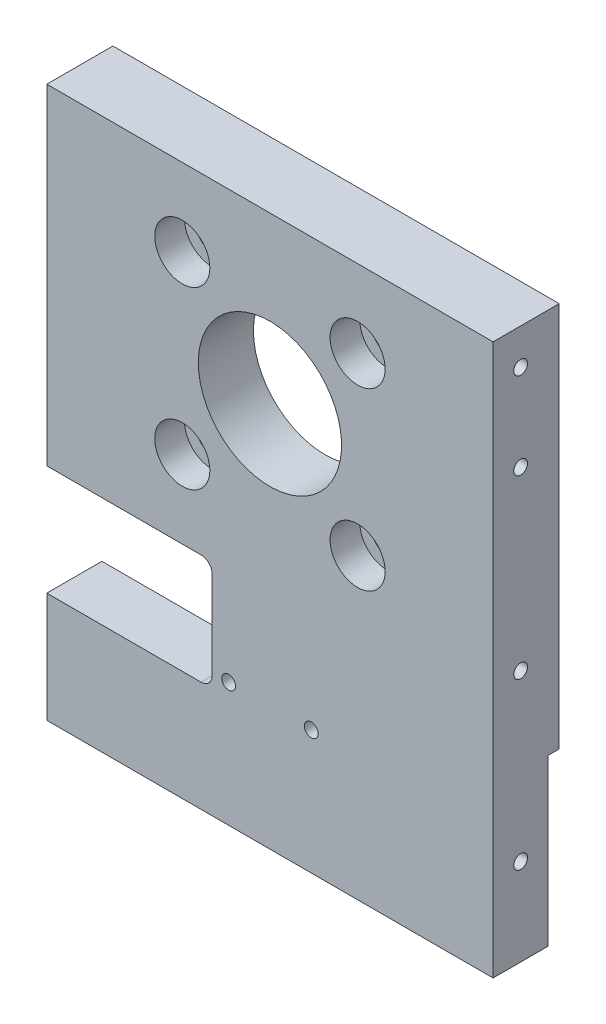
SolidWorks part; units mm, degrees
material "6061 合金"
ref_plane "前视基准面" through (0, 0, 0) normal (0, 0, 1) x (1, 0, 0)
ref_plane "上视基准面" through (0, 0, 0) normal (0, 1, 0) x (1, 0, 0)
ref_plane "右视基准面" through (0, 0, 0) normal (1, 0, 0) x (0, 0, -1)
sketch "草图1" plane through (0, 0, 0) normal (0, 0, 1) x (1, 0, 0)
  line L1 (-40.5, -50) -> (40.5, -50)
  line L2 (-40.5, -50) -> (-40.5, 50)
  line L3 (-40.5, 50) -> (40.5, 50)
  line L4 (40.5, -50) -> (40.5, 50)
  line L5 (-40.5, -50) -> (40.5, 50) construction
  line L6 (-40.5, 50) -> (40.5, -50) construction
  point P0 (0, 0)
  dimension "D1" = 81
  dimension "D2" = 100
extrude "凸台-拉伸1" add sketch "草图1" along normal blind 12
sketch "草图2" plane through (0, 0, 0) normal (0, 0, -1) x (-1, 0, 0)
  line L0 (-40.5, 50) -> (40.5, 50) construction
  circle A0 centre (0, 20) radius 13
  dimension "D1" = 26
  dimension "D2" = 30
extrude "切除-拉伸1" cut sketch "草图2" against normal through all
hole_wizard "M5 六角凹头螺钉的柱形沉头孔1" positions "草图6" profile "草图5" counterbore size "M5" standard "Iso" end condition through all
sketch "草图6" plane through (0, 0, 12) normal (0, 0, 1) x (1, 0, 0)
  line L1 (-15.9099, 4.0901) -> (15.9099, 4.0901) construction
  line L2 (-15.9099, 4.0901) -> (-15.9099, 35.9099) construction
  line L3 (-15.9099, 35.9099) -> (15.9099, 35.9099) construction
  line L4 (15.9099, 4.0901) -> (15.9099, 35.9099) construction
  line L5 (-15.9099, 4.0901) -> (15.9099, 35.9099) construction
  line L6 (-15.9099, 35.9099) -> (15.9099, 4.0901) construction
  point P0 (-15.9099, 35.9099)
  point P2 (15.9099, 35.9099)
  point P4 (15.9099, 4.0901)
  point P6 (-15.9099, 4.0901)
  point P25 (0, 20)
  dimension "D5" = 45
  dimension "D6" = 90
sketch "草图5" plane through (-15.9099, 35.9099, 12) normal (1, 0, 0) x (0, -1, 0)
  line L0 (0, 0) -> (0, 12)
  line L1 (0, 12) -> (2.75, 12)
  line L3 (2.75, 12) -> (2.75, 5.4)
  line L4 (2.75, 5.4) -> (5, 5.4)
  line L5 (5, 5.4) -> (5, 0)
  line L7 (5, 0) -> (0, 0)
  line L11 (0, -6.35) -> (0, 107.95) construction
  dimension "通孔孔直径" = 5.5
  dimension "通孔孔深度" = 12
  dimension "柱形沉头孔直径" = 10
  dimension "柱形沉头孔深度" = 5.4
hole_wizard "M3 螺纹孔1" positions "草图8" profile "草图7" tap size "M3" standard "Gb"
sketch "草图8" plane through (-40.5, 0, 0) normal (-1, 0, 0) x (0, 0, 1)
  line L0 (12, 50) -> (0, 50) construction
  line L1 (12, 50) -> (12, -50) construction
  point P0 (7, 43.5)
  point P2 (7, 27.8)
  point P4 (7, -4.2)
  point P6 (7, -34.2)
  dimension "D1" = 6.5
  dimension "D2" = 15.7
  dimension "D3" = 32
  dimension "D4" = 30
  dimension "D5" = 5
sketch "草图7" plane through (-40.5, 43.5, 7) normal (0, 1, 0) x (0, 0, 1)
  line L0 (0, 0) -> (0, 8.2511)
  line L1 (0, 8.2511) -> (1.25, 7.5)
  line L2 (1.25, 7.5) -> (1.25, 0)
  line L5 (1.25, 0) -> (0, 0)
  line L10 (0, 8.2511) -> (-1.25, 7.5) construction
  line L11 (0, -6.35) -> (0, 107.95) construction
  dimension "螺纹孔钻头直径" = 2.5
  dimension "螺纹孔钻头深度" = 7.5
  dimension "导头角度" = 118
cosmetic thread "孔螺蚊线1" parameters "D1"=6, "D2"=3
cosmetic thread "孔螺蚊线2" parameters "D1"=6, "D2"=3
cosmetic thread "孔螺蚊线3" parameters "D1"=6, "D2"=3
cosmetic thread "孔螺蚊线4" parameters "D1"=6, "D2"=3
mirror "镜向1" about plane through (0, 0, 0) normal (1, 0, 0) of "M3 螺纹孔1"
sketch "草图9" plane through (0, 0, 0) normal (0, 0, -1) x (-1, 0, 0)
  circle A0 centre (0, 20) radius 16.5
extrude "切除-拉伸2" cut sketch "草图9" against normal blind 2
sketch "草图10" plane through (0, 0, 0) normal (0, 0, -1) x (-1, 0, 0)
  line L0 (40.5, 50) -> (40.5, -50) construction
  line L1 (-40.5, -50) -> (40.5, -50)
  line L2 (-40.5, -50) -> (-40.5, -20)
  line L3 (-40.5, -20) -> (40.5, -20)
  line L4 (40.5, -50) -> (40.5, -20)
  dimension "D1" = 30
extrude "切除-拉伸3" cut sketch "草图10" against normal blind 2
sketch "草图11" plane through (0, 0, 0) normal (0, 0, -1) x (-1, 0, 0)
  line L0 (40.5, 50) -> (40.5, -20) construction
  line L1 (-40.5, 50) -> (40.5, 50) construction
  line L3 (10.5, -10) -> (70.5, -10)
  line L4 (10.5, -10) -> (10.5, -30)
  line L5 (10.5, -30) -> (70.5, -30)
  line L6 (70.5, -10) -> (70.5, -30)
  line L7 (10.5, -10) -> (70.5, -30) construction
  line L8 (10.5, -30) -> (70.5, -10) construction
  circle A0 centre (40.5, -20) radius 10 construction
  dimension "D1" = 20
  dimension "D2" = 70
  dimension "D3" = 20
  dimension "D4" = 30
extrude "切除-拉伸4" cut sketch "草图11" against normal blind 84
fillet "圆角1" radius 2 2 edges at (-10.5, -30, 7) (-10.5, -10, 6)
hole_wizard "M3 螺纹孔2" positions "草图14" profile "草图13" tap size "M3" standard "Gb"
sketch "草图14" plane through (0, 0, 12) normal (0, 0, 1) x (1, 0, 0)
  point P0 (7.5, -27.5)
  point P2 (-7.5, -27.5)
sketch "草图13" plane through (7.5, -27.5, 12) normal (1, 0, 0) x (0, -1, 0)
  line L0 (0, 0) -> (0, 8.2511)
  line L1 (0, 8.2511) -> (1.25, 7.5)
  line L2 (1.25, 7.5) -> (1.25, 0)
  line L5 (1.25, 0) -> (0, 0)
  line L10 (0, 8.2511) -> (-1.25, 7.5) construction
  line L11 (0, -6.35) -> (0, 107.95) construction
  dimension "螺纹孔钻头直径" = 2.5
  dimension "螺纹孔钻头深度" = 7.5
  dimension "导头角度" = 118
cosmetic thread "孔螺蚊线5" parameters "D1"=6, "D2"=3
cosmetic thread "孔螺蚊线6" parameters "D1"=6, "D2"=3
